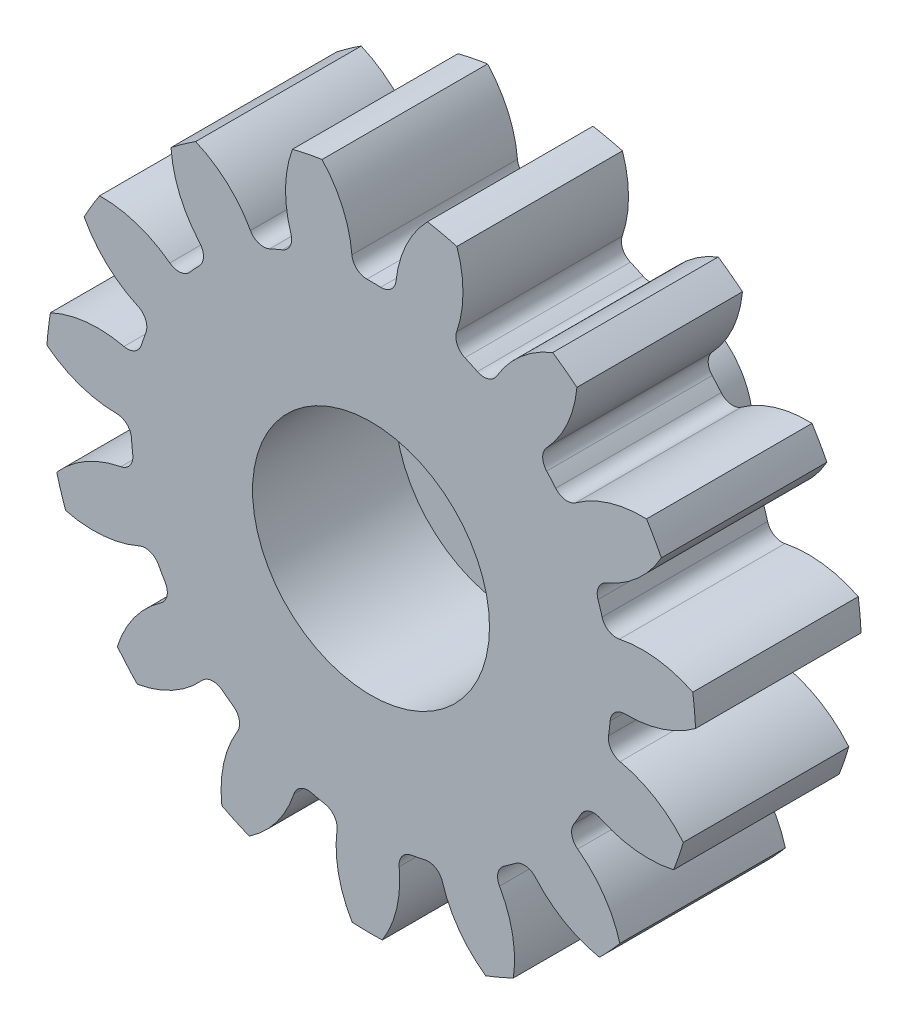
SolidWorks part; units mm, degrees
material "ABS"
ref_plane "Front" through (0, 0, 0) normal (0, 0, 1) x (1, 0, 0)
ref_plane "Top" through (0, 0, 0) normal (0, 1, 0) x (1, 0, 0)
ref_plane "Right" through (0, 0, 0) normal (1, 0, 0) x (0, 0, -1)
sketch "Sketch3" plane through (0, 0, 0) normal (0, 0, 1) x (1, 0, 0)
  circle A0 centre (0, 0) radius 21.59
  dimension "od" = 43.18
extrude "gearBody" add sketch "Sketch3" along normal blind 11
sketch "Sketch2" plane through (0, 0, 0) normal (0, 0, 1) x (1, 0, 0)
  line L0 (0, 0) -> (17.0393, 7.0579) construction
  line L1 (22.0105, -8.0941) -> (0, 0) construction
  line L2 (0, 0) -> (36.3143, 0) construction
  line L3 (19.0486, -0.229) -> (18.5878, -4.1711) construction
  line L5 (18.8182, -2.2) -> (0, 0) construction
  line L7 (0, 0) -> (18.4432, 0) construction
  arc A0 (18.4395, -0.3701) -> (18.0276, -3.8932) centre (0, 0) ccw construction
  arc A1 (21.5666, 1.0048) -> (20.7532, -5.9524) centre (0, 0) ccw construction
  arc A2 (19.0486, -0.229) -> (18.5878, -4.1711) centre (0, 0) ccw construction
  arc A3 (15.7838, -2.3046) -> (15.8898, -1.3984) centre (0, 0) ccw
  arc A4 (22.0105, -8.0941) -> (16.5506, -3.4102) centre (14.9518, -10.798) ccw
  arc A5 (22.0105, -8.0941) -> (23.2839, 2.7987) centre (0, 0) ccw
  arc A6 (23.2839, 2.7987) -> (16.8909, -0.4995) centre (17.0393, 7.0579) cw
  arc A7 (15.8898, -1.3984) -> (16.8909, -0.4995) centre (16.8715, -1.4848) cw
  arc A8 (16.5506, -3.4102) -> (15.7838, -2.3046) centre (16.759, -2.4469) cw
  point P6 (23.2839, 2.7987)
  point P22 (22.0105, -8.0941)
  dimension "baseDia" = 36.8864
  dimension "od" = 43.18
  dimension "pd" = 38.1
  dimension "rd" = 31.9024
  dimension "rFillet" = 0.9855
  dimension "pointX" = 23.2839
  dimension "pointY" = 2.7987
  dimension "CTT" = 3.9421
  dimension "flankCenterAngle" = 22.5
extrude "toothCut" cut sketch "Sketch2" along normal through all
pattern_circular "CirPattern1" count 15 over 360 about axis through (0, 0, 11) along (0, 0, -1) of "toothCut"
sketch "hub1Dia" plane through (0, 0, 0) normal (0, 0, -1) x (-1, 0, 0)
  circle A0 centre (0, 0) radius 12.7
  dimension "hub1Dia" = 25.4
sketch "hub2Dia" plane through (0, 0, 11) normal (0, 0, 1) x (1, 0, 0)
  circle A0 centre (0, 0) radius 12.7
  dimension "hub2dia" = 25.4
sketch "boreDia" plane through (0, 0, 0) normal (0, 0, 1) x (1, 0, 0)
  circle A0 centre (0, 0) radius 7.874
  dimension "boreDia" = 15.748
extrude "bore" cut sketch "boreDia" against normal mid plane 25400
sketch "Sketch4" plane through (0, 0, 0) normal (1, 0, 0) x (0, 0, -1)
  line L0 (0, 0) -> (29.4347, 0) construction
  line L1 (0, 0) -> (9.525, 0)
  line L2 (9.525, 0) -> (9.525, 4.826)
  line L3 (9.525, 4.826) -> (5.588, 4.826)
  line L4 (0, 0) -> (-1.524, 0)
  line L5 (-1.524, 0) -> (-1.524, 7.874)
  line L6 (-1.524, 7.874) -> (0, 7.874)
  line L7 (0, 12.2181) -> (0, 16.6995) construction
  line L8 (0, 7.874) -> (0, 10.414)
  arc A0 (0, 10.414) -> (5.588, 4.826) centre (5.588, 10.414) ccw
  point P3 (0, 13.9349)
  point P12 (0, 0)
  point P15 (3.1078, 4.7206)
  point P16 (0, 6.7322)
  dimension "D3" = 5.588
  dimension "D1" = 15.748
  dimension "D2" = 9.652
  dimension "D4" = 1.524
  dimension "D5" = 9.525
revolve "Revolve1" add sketch "Sketch4" angle 360 about L0
sketch "Sketch6" plane through (0, 0, -9.525) normal (0, 0, -1) x (-1, 0, 0)
  circle A0 centre (0, 0) radius 4.1
  dimension "D1" = 8.2
extrude "Cut-Extrude1" cut sketch "Sketch6" against normal blind 5.3
equation "\"Mid_Tube_Length\" = 1in"
equation "\"Bodytube_OD\" = 6.17in"
equation "\"Bodytube_ID\" = 5.998in"
equation "\"Camera_Cutout_Width\"=10mm"
equation "\"Camera_Cutout_Height\"=7mm"
equation "\"Fwd_Tube_Length\" = 40in"
equation "\"BKHD_Screw_Diam\"= 3.5mm"
equation "\"Fwd_BKHD_From_Top\" = 18in"
equation "\"Shear_Screw_Diameter\" = 0.086in"
equation "\"Shear_Screw_Coupler_Location\" = 4.5in"
equation "\"Motor_OD\" = 4in"
equation "\"Mid_Coupler_Length\" = 13in"
equation "\"Aft_Section_Length\"= 39in"
equation "\"AB_Coupler_OD_Length\"= 1in"
equation "\"AB_Coupling_Section_Length\"= 0.375in"
equation "\"AB_Coupler_Length\"= \"AB_Coupler_OD_Length\" + \"AB_Coupling_Section_Length\" * 2"
equation "\"Cutout_Angle\" = 80"
equation "\"AB_Paddle_Height\" = 0.375in"
equation "\"AB_Coupler_Num_Screws\"= 4"
equation "\"AB_BKHD_Thickness\" = 0.375in"
equation "\"AB_Mount_From_Bottom\" = 23.175in"
equation "\"Num_Cutouts\" = 3"
equation "\"AB_Coupler_OD\"= 6.17in"
equation "\"AB_Coupler_ID\"= 5.75in"
equation "\"AB_Coupler_Surface_Diameter\"= 5.998in"
equation "\"AB_Coupling_Screw_Diameter\"= 0.15748in"
equation "\"AB_Central_Bushing_Length\" = .4724in"
equation "\"Lead_Screw_Dist\" = 3.4in"
equation "\"Lead_Screw_Diam\" = 0.386in"
equation "\"Lead_Screw_Length\" = (\"Mid_Coupler_Length\" + 2*0.375in + 2*0.5in)"
equation "\"Paddle_Pin_Offset\" = .25in"
equation "\"Paddle_Pin_Radius\" = 2.25in"
equation "\"SS_Paddle_Pin_Radius\" = 2.25*0.66in"
equation "\"Paddle_Gear_OD\" = 3.2in"
equation "\"Drive_Gear_OD\" = 1.7in"
equation "\"Fin_Thickness\"= .118in"
equation "\"Guiderail_Cutout_Diameter\"= 1.5in"
equation "\"DB9_Hole_Dist\" = 25mm"
equation "\"DB9_Relief_Width\" = 0.47in"
equation "\"DB9_Relief_Hole_Offset\" = 0.09in"
equation "\"Airbrakes_Wire_Hole_Dia\" = .25in"
equation "\"Airbrakes_Wire_Hole_Dist\" = 1.1in"
equation "\"Servo_Gear_Offset\" = 0.5in"
equation "\"FWD_Shear_Screw_Dist\" = 1.5in"
equation "\"Camera_Screw_Dia\" = 0.216535"
equation "\"Camera_Hole_Angle\" = atn ( 2 / 3 * tan ( 12.5deg ) )"
equation "\"Coupler_OD\" = 5.998"
equation "\"Coupler_ID\" = 5.8"
equation "\"Mounting_Bracket_Centerhole_DIA\" = 0.4in"
equation "\"Drive_Gear_Shaft_DIA\" = \"Mounting_Bracket_Centerhole_DIA\" - 0.02in"
equation "\"Drive_Gear_Fillet\" = 0.22in"
equation "\"Drive_Gear_ID\" = 0.62in"
equation "\"Drive_Gear_Offset\" = 0.01in"
equation "\"D2@Sketch4\"=\"Drive_Gear_Shaft_DIA\""
equation "\"D1@Sketch4\"=\"Drive_Gear_ID\""
equation "\"D3@Sketch4\"=\"Drive_Gear_Fillet\""
